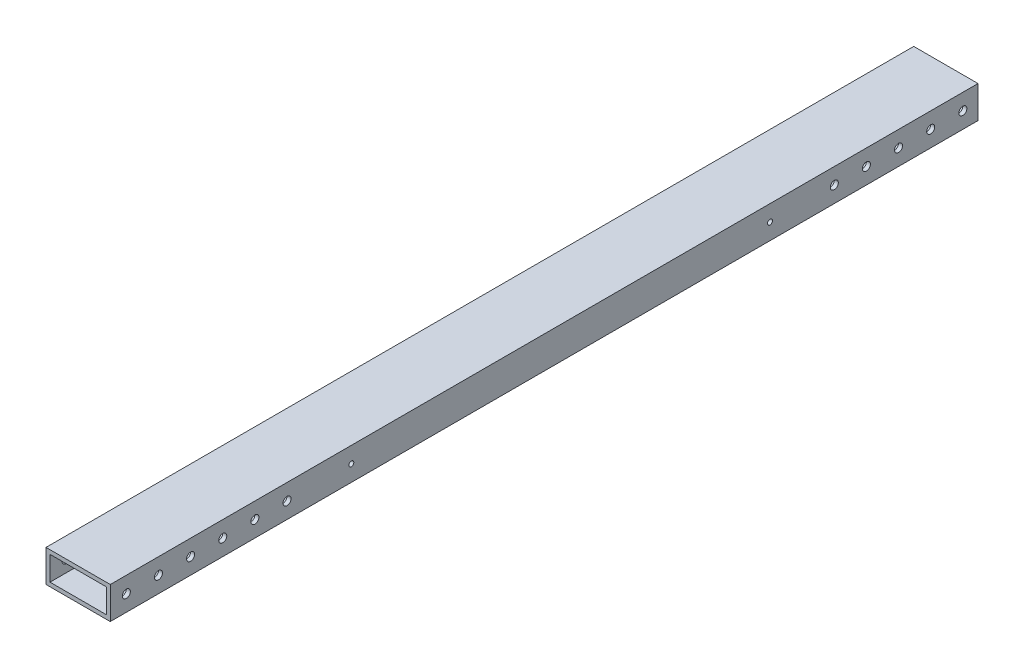
SolidWorks part; units mm, degrees
material "6061 Alloy"
ref_plane "Front Plane" through (0, 0, 0) normal (0, 0, 1) x (1, 0, 0)
ref_plane "Top Plane" through (0, 0, 0) normal (0, 1, 0) x (1, 0, 0)
ref_plane "Right Plane" through (0, 0, 0) normal (1, 0, 0) x (0, 0, -1)
sketch "Sketch1" plane through (0, 0, 0) normal (0, 0, 1) x (1, 0, 0)
  line L0 (-22.225, 9.525) -> (22.225, 9.525)
  line L2 (-25.4, 12.7) -> (25.4, 12.7)
  line L3 (-25.4, 12.7) -> (-25.4, -12.7)
  line L4 (-25.4, -12.7) -> (25.4, -12.7)
  line L5 (25.4, 12.7) -> (25.4, -12.7)
  line L10 (22.225, 9.525) -> (22.225, -9.525)
  line L11 (-22.225, -9.525) -> (22.225, -9.525)
  line L12 (-22.225, 9.525) -> (-22.225, -9.525)
  point P12 (0, 12.7)
  point P14 (25.4, 0)
  dimension "Wall Thickness" = 3.175
  dimension "Outside Width" = 50.8
  dimension "Outside Height" = 25.4
  dimension "Inside Height" = 19.05
  dimension "Inside Width" = 44.45
sketch "Sketch2" plane through (0, 0, 0) normal (1, 0, 0) x (0, 0, -1)
  line L0 (342.9, 0) -> (-342.9, 0)
  point P4 (0, 0)
  point P7 (-342.9, 0)
  point P10 (342.9, 0)
  dimension "Length" = 685.8
sketch "Sketch3" plane through (0, 0, 0) normal (0, 0, 1) x (1, 0, 0)
  line L21 (25.4, 12.7) -> (-25.4, 12.7)
  line L22 (25.4, -12.7) -> (25.4, 12.7)
  line L23 (-25.4, -12.7) -> (25.4, -12.7)
  line L24 (-25.4, 12.7) -> (-25.4, -12.7)
  line L25 (25.4, 12.7) -> (-25.4, 12.7)
  line L26 (25.4, -12.7) -> (25.4, 12.7)
  line L27 (-25.4, -12.7) -> (25.4, -12.7)
  line L28 (-25.4, 12.7) -> (-25.4, -12.7)
  line L29 (22.225, 9.525) -> (-22.225, 9.525)
  line L30 (22.225, -9.525) -> (22.225, 9.525)
  line L31 (-22.225, -9.525) -> (22.225, -9.525)
  line L32 (-22.225, 9.525) -> (-22.225, -9.525)
  line L33 (22.225, 9.525) -> (-22.225, 9.525)
  line L34 (22.225, -9.525) -> (22.225, 9.525)
  line L35 (-22.225, -9.525) -> (22.225, -9.525)
  line L36 (-22.225, 9.525) -> (-22.225, -9.525)
  dimension "D1" = 0
  dimension "D2" = 0
extrude "Boss-Extrude1" add sketch "Sketch3" along normal up to vertex (342.9 mm away) and the other way up to vertex (342.9 mm away) up to point (0, 0, 342.9) other way up to point (0, 0, -342.9)
sketch "Drawing Reference" plane through (0, 0, 0) normal (1, 0, 0) x (0, 0, -1)
  line L0 (-342.9, 0) -> (342.9, 0) construction
  line L1 (0, -12.7) -> (0, 12.7) construction
  line L2 (-342.9, -12.7) -> (342.9, -12.7) construction
  line L5 (-342.9, 12.7) -> (342.9, 12.7) construction
  point P7 (-306.324, 0)
  point P8 (306.324, 0)
  dimension "D1" = 36.576
sketch "Sketch5" plane through (25.4, 0, 0) normal (1, 0, 0) x (0, 0, -1)
  line L0 (-342.9, 0) -> (-279.4, 0)
  line L1 (-342.9, -12.7) -> (-342.9, 12.7) construction
  line L2 (-279.4, 0) -> (-254, 0)
  line L3 (-254, 0) -> (-228.6, 0)
  line L4 (-228.6, 0) -> (-203.2, 0)
sketch "Sketch8" plane through (25.4, 0, 0) normal (1, 0, 0) x (0, 0, -1)
  line L0 (342.9, 0) -> (305.5118, 0)
  line L1 (342.9, -12.7) -> (342.9, 12.7) construction
  line L2 (305.5118, 0) -> (280.1118, 0)
  line L3 (280.1118, 0) -> (254.7118, 0)
  line L4 (254.7118, 0) -> (229.3118, 0)
hole_wizard "1/4 (0.25) Diameter Hole3" positions "Sketch12" profile "Sketch13" hole size "1/4" standard "ANSI Inch" end condition through all
sketch "Sketch12" plane through (-25.4, 0, 0) normal (-1, 0, 0) x (0, 0, 1)
  point P0 (-330.9118, 0)
sketch "Sketch13" plane through (-25.4, 0, -330.9118) normal (0, 1, 0) x (0, 0, 1)
  line L0 (0, 0) -> (0, 50.8)
  line L1 (0, 50.8) -> (3.175, 50.8)
  line L2 (3.175, 50.8) -> (3.175, 0)
  line L5 (3.175, 0) -> (0, 0)
  line L11 (0, -6.35) -> (0, 107.95) construction
  dimension "Thru Hole Dia." = 6.35
  dimension "Thru Hole Depth" = 50.8
hole_wizard "1/4 (0.25) Diameter Hole4" positions "Sketch14" profile "Sketch15" hole size "1/4" standard "ANSI Inch" end condition through all
sketch "Sketch14" plane through (-25.4, 0, 0) normal (-1, 0, 0) x (0, 0, 1)
  point P0 (304.8, 0)
  point P3 (330.2, 0)
sketch "Sketch15" plane through (-25.4, 0, 304.8) normal (0, 1, 0) x (0, 0, 1)
  line L0 (0, 0) -> (0, 50.8)
  line L1 (0, 50.8) -> (3.175, 50.8)
  line L2 (3.175, 50.8) -> (3.175, 0)
  line L5 (3.175, 0) -> (0, 0)
  line L11 (0, -6.35) -> (0, 107.95) construction
  dimension "Thru Hole Dia." = 6.35
  dimension "Thru Hole Depth" = 50.8
hole_wizard "1/4 (0.25) Diameter Hole5" positions "Sketch17" profile "Sketch18" hole size "1/4" standard "ANSI Inch" end condition through all
sketch "Sketch17" plane through (25.4, 0, 0) normal (1, 0, 0) x (0, 0, -1)
  point P0 (305.5118, 0)
  point P3 (280.1118, 0)
sketch "Sketch18" plane through (25.4, 0, -305.5118) normal (0, 1, 0) x (0, 0, -1)
  line L0 (0, 0) -> (0, 50.8)
  line L1 (0, 50.8) -> (3.175, 50.8)
  line L2 (3.175, 50.8) -> (3.175, 0)
  line L5 (3.175, 0) -> (0, 0)
  line L11 (0, -6.35) -> (0, 107.95) construction
  dimension "Thru Hole Dia." = 6.35
  dimension "Thru Hole Depth" = 50.8
hole_wizard "1/4 (0.25) Diameter Hole6" positions "Sketch19" profile "Sketch20" hole size "1/4" standard "ANSI Inch" end condition through all
sketch "Sketch19" plane through (25.4, 0, 0) normal (1, 0, 0) x (0, 0, -1)
  point P0 (229.3118, 0)
  point P3 (254.7118, 0)
sketch "Sketch20" plane through (25.4, 0, -229.3118) normal (0, 1, 0) x (0, 0, -1)
  line L0 (0, 0) -> (0, 50.8)
  line L1 (0, 50.8) -> (3.175, 50.8)
  line L2 (3.175, 50.8) -> (3.175, 0)
  line L5 (3.175, 0) -> (0, 0)
  line L11 (0, -6.35) -> (0, 107.95) construction
  dimension "Thru Hole Dia." = 6.35
  dimension "Thru Hole Depth" = 50.8
hole_wizard "1/4 (0.25) Diameter Hole7" positions "Sketch21" profile "Sketch22" hole size "1/4" standard "ANSI Inch" end condition through all
sketch "Sketch21" plane through (25.4, 0, 0) normal (1, 0, 0) x (0, 0, -1)
  point P0 (-203.2, 0)
  point P3 (-228.6, 0)
sketch "Sketch22" plane through (25.4, 0, 203.2) normal (0, 1, 0) x (0, 0, -1)
  line L0 (0, 0) -> (0, 50.8)
  line L1 (0, 50.8) -> (3.175, 50.8)
  line L2 (3.175, 50.8) -> (3.175, 0)
  line L5 (3.175, 0) -> (0, 0)
  line L11 (0, -6.35) -> (0, 107.95) construction
  dimension "Thru Hole Dia." = 6.35
  dimension "Thru Hole Depth" = 50.8
hole_wizard "1/4 (0.25) Diameter Hole8" positions "Sketch23" profile "Sketch24" hole size "1/4" standard "ANSI Inch" end condition through all
sketch "Sketch23" plane through (25.4, 0, 0) normal (1, 0, 0) x (0, 0, -1)
  point P0 (-279.4, 0)
  point P3 (-254, 0)
sketch "Sketch24" plane through (25.4, 0, 279.4) normal (0, 1, 0) x (0, 0, -1)
  line L0 (0, 0) -> (0, 50.8)
  line L1 (0, 50.8) -> (3.175, 50.8)
  line L2 (3.175, 50.8) -> (3.175, 0)
  line L5 (3.175, 0) -> (0, 0)
  line L11 (0, -6.35) -> (0, 107.95) construction
  dimension "Thru Hole Dia." = 6.35
  dimension "Thru Hole Depth" = 50.8
sketch "Sketch25" plane through (25.4, 0, 0) normal (1, 0, 0) x (0, 0, -1)
  line L0 (-203.2, 0) -> (-152.4, 0)
  line L1 (229.3118, 0) -> (178.5118, 0)
hole_wizard "5/32 (0.15625) Diameter Hole1" positions "Sketch26" profile "Sketch27" hole size "5/32" standard "ANSI Inch" end condition through all
sketch "Sketch26" plane through (25.4, 0, 0) normal (1, 0, 0) x (0, 0, -1)
  point P0 (-152.4, 0)
  point P3 (178.5118, 0)
sketch "Sketch27" plane through (25.4, 0, 152.4) normal (0, 1, 0) x (0, 0, -1)
  line L0 (0, 0) -> (0, 50.8)
  line L1 (0, 50.8) -> (1.9844, 50.8)
  line L2 (1.9844, 50.8) -> (1.9844, 0)
  line L5 (1.9844, 0) -> (0, 0)
  line L11 (0, -6.35) -> (0, 107.95) construction
  dimension "Thru Hole Dia." = 3.9688
  dimension "Thru Hole Depth" = 50.8
sketch "Sketch28" plane through (-25.4, 0, 0) normal (-1, 0, 0) x (0, 0, 1)
  line L0 (102.8316, 0) -> (77.4316, 0)
  line L1 (-103.5434, 0) -> (-128.9434, 0)
hole_wizard "1/2 (0.5) Diameter Hole1" positions "Sketch29" profile "Sketch30" hole size "1/2" standard "ANSI Inch"
sketch "Sketch29" plane through (-25.4, 0, 0) normal (-1, 0, 0) x (0, 0, 1)
  point P1 (-591.3016, -480.8022)
  point P3 (-103.5434, 0)
  point P6 (77.4316, 0)
  point P9 (102.8316, 0)
  point P13 (-128.9434, 0)
sketch "Sketch30" plane through (-25.4, -480.8022, -591.3016) normal (0, 1, 0) x (0, 0, 1)
  line L0 (0, 0) -> (0, 10.1655)
  line L1 (0, 10.1655) -> (6.35, 6.35)
  line L2 (6.35, 6.35) -> (6.35, 0)
  line L5 (6.35, 0) -> (0, 0)
  line L10 (0, 10.1655) -> (-6.35, 6.35) construction
  line L11 (0, -6.35) -> (0, 107.95) construction
  dimension "Hole Dia." = 12.7
  dimension "Hole Depth" = 6.35
  dimension "Drill Angle" = 118
equation "\"D1@Drawing Reference\"=\"Outside Width@Sketch1\" * 0.72"
